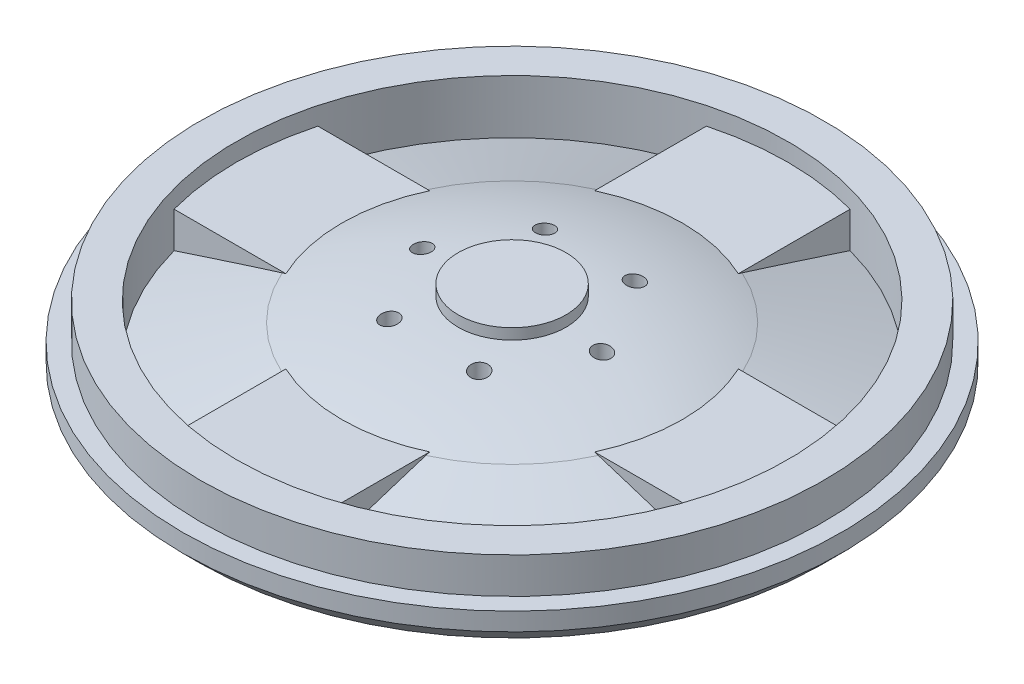
SolidWorks part; units mm, degrees
ref_plane "Front" through (0, 0, 0) normal (0, 0, 1) x (1, 0, 0)
ref_plane "Top" through (0, 0, 0) normal (0, 1, 0) x (1, 0, 0)
ref_plane "Right" through (0, 0, 0) normal (1, 0, 0) x (0, 0, -1)
sketch "草图1" plane through (0, 0, 0) normal (0, 1, 0) x (1, 0, 0)
  circle A0 centre (0, 0) radius 9.17
  dimension "D1" = 18.34
extrude "凸台-拉伸1" add sketch "草图1" along normal blind 0.5
sketch "草图8" plane through (0, 0.5, 0) normal (0, 1, 0) x (1, 0, 0)
  circle A0 centre (0, 0) radius 9.17
  circle A1 centre (0, 0) radius 7.67
  circle A2 centre (0, 0) radius 9.17 construction
  dimension "D1" = 1.5
extrude "凸台-拉伸3" add sketch "草图8" along normal blind 0.5
sketch "草图14" plane through (0, 1, 0) normal (0, 1, 0) x (1, 0, 0)
  circle A0 centre (0, 0) radius 7.67
  circle A1 centre (0, 0) radius 8.67
  dimension "D1" = 1
extrude "凸台-拉伸9" add sketch "草图14" along normal blind 1
chamfer "倒角1" distance 0.5 angle 45 1 edges at (0, 0, 9.17)
sketch "草图15" plane through (0, 0.5, 0) normal (0, 1, 0) x (1, 0, 0)
  circle A0 centre (0, 0) radius 3
  dimension "D1" = 6
extrude "凸台-拉伸10" add sketch "草图15" along normal blind 1.6058
loft "放样1" add section edge at (0, 2.1058, 3) section edge at (0, 0.5, 7.67) connector at (1.0144, 2.1058, 2.8233) connector at (3.987, 0.5, 6.5523)
sketch "草图13" plane through (0, 0, 0) normal (0, -1, 0) x (1, 0, 0)
  line L0 (0, 17.9095) -> (0, -12.8328) construction
  line L1 (2.4927, 2) -> (2.4927, -2)
  line L2 (-2, 2.4927) -> (2, 2.4927)
  line L3 (-2, 2.4927) -> (-2, 8.0736)
  line L4 (-2, 8.0736) -> (2, 8.0736)
  line L5 (2, 2.4927) -> (2, 8.0736)
  line L6 (-2, 2.4927) -> (2, 8.0736) construction
  line L7 (-2, 8.0736) -> (2, 2.4927) construction
  line L8 (2.4927, 2) -> (8.0736, 2)
  line L9 (8.0736, 2) -> (8.0736, -2)
  line L10 (2.4927, -2) -> (8.0736, -2)
  line L11 (2.4927, 2) -> (8.0736, -2) construction
  line L12 (8.0736, 2) -> (2.4927, -2) construction
  line L13 (2, -2.4927) -> (-2, -2.4927)
  line L14 (2, -2.4927) -> (2, -8.0736)
  line L15 (2, -8.0736) -> (-2, -8.0736)
  line L16 (-2, -2.4927) -> (-2, -8.0736)
  line L17 (2, -2.4927) -> (-2, -8.0736) construction
  line L18 (2, -8.0736) -> (-2, -2.4927) construction
  line L19 (-2.4927, -2) -> (-2.4927, 2)
  line L20 (-2.4927, -2) -> (-8.0736, -2)
  line L21 (-8.0736, -2) -> (-8.0736, 2)
  line L22 (-2.4927, 2) -> (-8.0736, 2)
  line L23 (-2.4927, -2) -> (-8.0736, 2) construction
  line L24 (-8.0736, -2) -> (-2.4927, 2) construction
  point P3 (0, 5.2831)
  point P11 (5.2831, 0)
  point P16 (0, -5.2831)
  point P21 (-5.2831, 0)
  point P26 (0, 0)
  dimension "D1" = 4
  dimension "D2" = 4
extrude "凸台-拉伸8" add sketch "草图13" against normal blind 1.5
sketch "草图16" plane through (0, 2.1058, 0) normal (0, 1, 0) x (1, 0, 0)
  circle A0 centre (0, 0) radius 1.5
  dimension "D1" = 3
extrude "凸台-拉伸11" add sketch "草图16" along normal blind 0.3
fillet "圆角1" radius 12 1 edges at (0, 2.1058, 3)
sketch "草图17" plane through (0, 2.4058, 0) normal (0, 1, 0) x (1, 0, 0)
  line L0 (-11.3082, 0) -> (14.0386, 0) construction
  circle A0 centre (2.5, 0) radius 0.25
  dimension "D1" = 0.5
  dimension "D2" = 2.5
extrude "切除-拉伸1" cut sketch "草图17" against normal blind 1
pattern_circular "阵列(圆周)1" count 6 every 60 about axis through (0, 1.4677, 0) along (0, -1, 0) of "切除-拉伸1"
